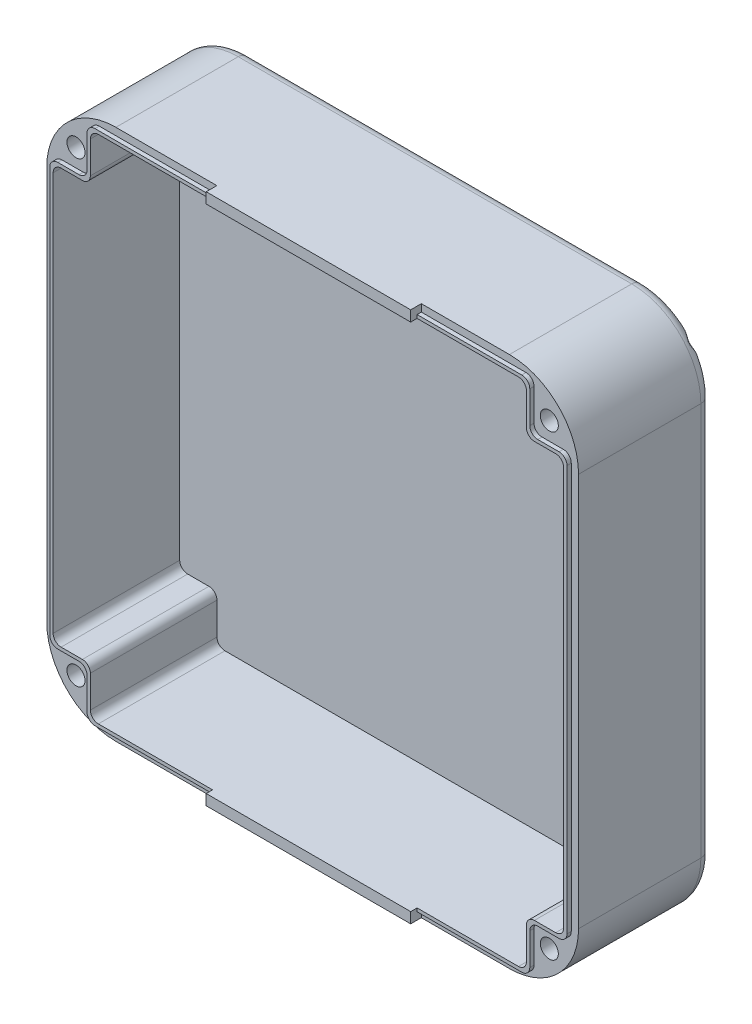
SolidWorks part; units mm, degrees
ref_plane "Спереди" through (0, 0, 0) normal (0, 0, 1) x (1, 0, 0)
ref_plane "Сверху" through (0, 0, 0) normal (0, 1, 0) x (1, 0, 0)
ref_plane "Справа" through (0, 0, 0) normal (1, 0, 0) x (0, 0, -1)
sketch "Sketch1" plane through (0, 0, 0) normal (0, 0, 1) x (1, 0, 0)
  line L1 (-50, 100) -> (50, 100) construction
  line L2 (-50, 100) -> (-50, 0) construction
  line L3 (-50, 0) -> (50, 0) construction
  line L5 (-50, 50) -> (30, 50) construction
  line L7 (0, 0) -> (0, 100) construction
  line L10 (-50, 100) -> (-50, 0) construction
  line L11 (-50, 100) -> (50, 100)
  line L12 (50, 100) -> (50, 0) construction
  line L13 (50, 0) -> (-50, 0)
  line L20 (50, 0) -> (50, 19)
  line L21 (50, 19) -> (50, 100)
  line L22 (-50, 0) -> (-50, 19)
  line L23 (-50, 19) -> (-50, 100)
  dimension "D1" = 100
  dimension "D2" = 100
extrude "Boss-Extrude1" add sketch "Sketch1" along normal blind 25
shell "Shell1" thickness 2 removed face at (0, 50, 25)
sketch "Sketch3" plane through (0, 0, 2) normal (0, 0, 1) x (1, 0, 0)
  line L0 (0, 0) -> (0, 100) construction
  line L1 (48, 2) -> (41, 2)
  line L2 (48, 2) -> (48, 11)
  line L3 (48, 11) -> (41, 11)
  line L4 (41, 2) -> (41, 11)
  line L5 (-50, 0) -> (50, 0) construction
  line L6 (50, 100) -> (-50, 100) construction
  line L7 (-41, 2) -> (-41, 11)
  line L8 (48, 2) -> (48, 98) construction
  line L9 (48, 50) -> (-48, 50) construction
  line L10 (-48, 98) -> (-48, 2) construction
  line L11 (-48, 11) -> (-41, 11)
  line L12 (-48, 2) -> (-48, 11)
  line L13 (-48, 2) -> (-41, 2)
  line L14 (-48, 98) -> (-41, 98)
  line L15 (-48, 98) -> (-48, 89)
  line L16 (-48, 89) -> (-41, 89)
  line L17 (-41, 98) -> (-41, 89)
  line L18 (41, 98) -> (41, 89)
  line L19 (48, 89) -> (41, 89)
  line L20 (48, 98) -> (48, 89)
  line L21 (48, 98) -> (41, 98)
  line L22 (50, 0) -> (50, 100) construction
  circle A0 centre (44.5, 7) radius 1.7
  circle A1 centre (-44.5, 7) radius 1.7
  circle A2 centre (-44.5, 93) radius 1.7
  circle A3 centre (44.5, 93) radius 1.7
  dimension "D3" = 3.4
  dimension "D1" = 7
  dimension "D2" = 9
  dimension "D4" = 7
  dimension "D5" = 5.5
extrude "Boss-Extrude3" add sketch "Sketch3" along normal up to surface (23 mm away) up to face at (0, 50, 25)
sketch "Sketch5" plane through (0, 0, 25) normal (0, 0, 1) x (1, 0, 0)
  line L0 (0, 0) -> (0, 100) construction
  line L1 (-50, 0) -> (50, 0) construction
  line L2 (50, 100) -> (-50, 100) construction
  line L4 (48, 11) -> (48, 89) construction
  line L5 (48, 50) -> (-48, 50) construction
  line L6 (48, 11) -> (48, 89) construction
  line L7 (48.6274, 10.3726) -> (48.6274, 80.8983) construction
  line L8 (48, 11) -> (41, 11)
  line L9 (41, 11) -> (41, 2)
  line L10 (41, 2) -> (0, 2)
  line L11 (-41, 2) -> (41, 2) construction
  line L38 (50, 100) -> (-50, 100) construction
  line L42 (48, 11) -> (48, 50)
  line L49 (48.6274, 10.3726) -> (41.6274, 10.3726)
  line L50 (41.6274, 10.3726) -> (41.6274, 1.3726)
  line L51 (41.6274, 1.3726) -> (0, 1.3726)
  line L52 (-41.6274, 1.3726) -> (0, 1.3726)
  line L53 (-41.6274, 10.3726) -> (-41.6274, 1.3726)
  line L54 (-48.6274, 10.3726) -> (-41.6274, 10.3726)
  line L58 (-48, 11) -> (-48, 50)
  line L61 (-41, 2) -> (0, 2)
  line L62 (-41, 11) -> (-41, 2)
  line L63 (-48, 11) -> (-41, 11)
  line L64 (-48, 89) -> (-41, 89)
  line L65 (-41, 89) -> (-41, 98)
  line L66 (-41, 98) -> (0, 98)
  line L68 (-48, 89) -> (-48, 50)
  line L70 (-48.6274, 89.6274) -> (-48.6274, 10.3726)
  line L71 (-48.6274, 89.6274) -> (-41.6274, 89.6274)
  line L72 (-41.6274, 89.6274) -> (-41.6274, 98.6274)
  line L73 (-41.6274, 98.6274) -> (0, 98.6274)
  line L74 (41.6274, 98.6274) -> (0, 98.6274)
  line L75 (41.6274, 89.6274) -> (41.6274, 98.6274)
  line L76 (48.6274, 89.6274) -> (41.6274, 89.6274)
  line L77 (48.6274, 89.6274) -> (48.6274, 10.3726)
  line L80 (48, 89) -> (48, 50)
  line L83 (41, 98) -> (0, 98)
  line L84 (41, 89) -> (41, 98)
  line L85 (48, 89) -> (41, 89)
  line L86 (42.6274, -66.7738) -> (42.6274, 29) construction
  line L87 (48.6274, 80.8983) -> (42.6274, -66.7738) construction
  line L88 (48, 50) -> (42, -97.6721) construction
  line L89 (42, -97.6721) -> (42, 29) construction
  dimension "D1" = 50
extrude "Boss-Extrude4" add sketch "Sketch5" along normal blind 0.8
fillet "Fillet6" radius 1.5 12 edges at (-41, 2, 13.9) (-41, 11, 13.9) (-48, 11, 13.9) (-48, 89, 13.9) (-41, 89, 13.9) (-41, 98, 13.9) (41, 98, 13.9) (41, 89, 13.9) (48, 89, 13.9) (41, 2, 13.9) (48, 11, 13.9) (41, 11, 13.9)
fillet "Fillet7" radius 1.5 12 edges at (41.6274, 10.3726, 25.4) (41.6274, 1.3726, 25.4) (-41.6274, 1.3726, 25.4) (-41.6274, 10.3726, 25.4) (-48.6274, 89.6274, 25.4) (-41.6274, 89.6274, 25.4) (-41.6274, 98.6274, 25.4) (41.6274, 98.6274, 25.4) (41.6274, 89.6274, 25.4) (48.6274, 89.6274, 25.4) (-48.6274, 10.3726, 25.4) (48.6274, 10.3726, 25.4)
sketch "Sketch6" plane through (50, 0, 0) normal (1, 0, 0) x (0, 0, -1)
  line L5 (-25, 0) -> (0, 0) construction
  line L7 (-25, 0) -> (-25, 100) construction
  circle A0 centre (-20, 29) radius 2.5
  dimension "D11" = 5
  dimension "D2" = 29
  dimension "D3" = 5
fillet "Fillet8" radius 13 4 edges at (-50, 0, 12.5) (-50, 100, 12.5) (50, 100, 12.5) (50, 0, 12.5)
fillet "Fillet11" radius 2 8 edges at (46.1924, 96.1924, 0) (50, 50, 0) (46.1924, 3.8076, 0) (0, 0, 0) (-46.1924, 3.8076, 0) (-50, 50, 0) (-46.1924, 96.1924, 0) (0, 100, 0)
ref_plane "Plane1" through (0, 50, 0) normal (0, -1, 0) x (-1, 0, 0)
ref_plane "Plane2" through (0, 0, 0) normal (1, 0, 0) x (0, 0, -1)
ref_plane "Plane3" through (0, 0, 7.5) normal (0, 0, 1) x (1, 0, 0)
sketch "Sketch17" plane through (0, 0, 0) normal (0, 0, -1) x (-1, 0, 0)
  line L0 (0, 0) -> (0, 100) construction
  line L2 (-37, 100) -> (37, 100) construction
  line L3 (0, 100) -> (48, 50) construction
  line L4 (48, 50) -> (-48, 50) construction
  line L5 (37, 0) -> (-37, 0) construction
  circle A0 centre (44.5, 7) radius 1.7
  circle A1 centre (-44.5, 7) radius 1.7
  circle A2 centre (-44.5, 93) radius 1.7
  circle A3 centre (44.5, 93) radius 1.7
  dimension "D1" = 3.4
extrude "Cut-Extrude5" cut sketch "Sketch17" against normal blind 10
sketch "Sketch18" plane through (0, 0, 0) normal (0, 0, -1) x (-1, 0, 0)
  line L0 (0, 0) -> (0, 100) construction
  line L1 (-50, 13) -> (-50, 87) construction
  line L2 (-37, 100) -> (37, 100) construction
  line L4 (50, 87) -> (50, 13) construction
  line L5 (50, 50) -> (-50, 50) construction
  circle A0 centre (44.5, 7) radius 2.5
  circle A1 centre (-44.5, 7) radius 2.5
  circle A2 centre (-44.5, 93) radius 2.5
  circle A3 centre (44.5, 93) radius 2.5
  dimension "D1" = 5
extrude "Cut-Extrude6" cut sketch "Sketch18" against normal blind 5
fillet "Fillet16" radius 0.4 8 edges at (-46.8011, 93.9773, 0.2862) (-45.9586, 4.9696, 0.2862) (-42.5478, 8.5617, 0) (46.8011, 6.0227, 0.2862) (42.5478, 91.4383, 0) (-42.5478, 91.4383, 0) (42.5478, 8.5617, 0) (45.9586, 95.0304, 0.2862)
ref_plane "Plane4" through (0, 19, 0) normal (0, -1, 0) x (-1, 0, 0)
ref_plane "Plane5" through (0, 0, 0) normal (1, 0, 0) x (0, 0, -1)
sketch "Sketch19" plane through (0, 0, 25) normal (0, 0, 1) x (1, 0, 0)
  line L0 (37, 100) -> (-37, 100) construction
  line L1 (20.4357, 100) -> (-18.0148, 100)
  line L2 (20.4357, 100) -> (20.4357, 98)
  line L3 (20.4357, 98) -> (-18.0148, 98)
  line L4 (-18.0148, 100) -> (-18.0148, 98)
  line L5 (39.5, 98) -> (-39.5, 98) construction
  line L6 (50, 50) -> (-50, 50) construction
  line L7 (50, 13) -> (50, 87) construction
  line L8 (-50, 87) -> (-50, 13) construction
  line L9 (-18.0148, 0) -> (-18.0148, 2)
  line L10 (20.4357, 2) -> (-18.0148, 2)
  line L11 (20.4357, 0) -> (20.4357, 2)
  line L12 (20.4357, 0) -> (-18.0148, 0)
extrude "Boss-Extrude5" add sketch "Sketch19" along normal blind 2
